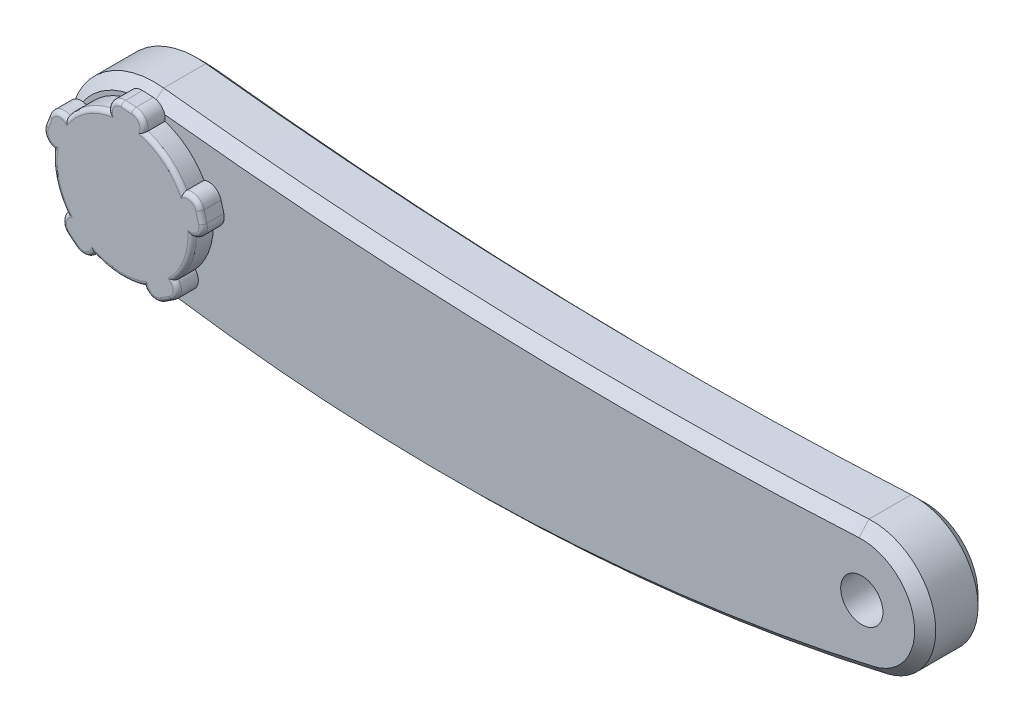
SolidWorks part; units mm, degrees
material "可锻铸铁"
ref_plane "前视基准面" through (0, 0, 0) normal (0, 0, 1) x (1, 0, 0)
ref_plane "上视基准面" through (0, 0, 0) normal (0, 1, 0) x (1, 0, 0)
ref_plane "右视基准面" through (0, 0, 0) normal (1, 0, 0) x (0, 0, -1)
sketch "草图1" plane through (0, 0, 0) normal (0, 0, 1) x (1, 0, 0)
  line L0 (-85, 0) -> (85, 0) construction
  circle A0 centre (-85, 0) radius 20
  circle A1 centre (85, 0) radius 15
  arc A2 (-82.7465, 19.8726) -> (84.1861, 14.9779) centre (29.9265, 1013.5048) ccw
  arc A3 (-88.3618, -19.7154) -> (88.3697, -14.6166) centre (-12.7206, 423.8817) ccw
  point P4 (0, 0)
  dimension "D2" = 30
  dimension "D3" = 40
  dimension "D4" = 450
  dimension "D5" = 1000
  dimension "D1" = 170
extrude "凸台-拉伸1" add sketch "草图1" along normal mid plane 15 contours A0 L0 A1 A2 | L0 A0 A3 A1 | A0 | A1 region at (-1.0237, 7.6812, 0) region at (-72.4659, -14.8523, 0) region at (-0.4487, -12.3679, 0) region at (74.4175, 10.0231, 0)
chamfer "倒角1" distance 2.5 angle 45 8 edges at (99.8523, 2.0996, -7.5) (0.6174, 13.9344, -7.5) (-104.8018, 2.8087, -7.5) (0.2568, -25.9311, -7.5) (-104.8018, 2.8087, 7.5) (0.6174, 13.9344, 7.5) (99.8523, 2.0996, 7.5) (0.2568, -25.9311, 7.5)
sketch "草图3" plane through (0, 0, 7.5) normal (0, 0, 1) x (1, 0, 0)
  circle A0 centre (-85, 0) radius 16.5
  dimension "D1" = 33
extrude "凸台-拉伸2" add sketch "草图3" along normal blind 5
sketch "草图4" plane through (0, 0, 12.5) normal (0, 0, 1) x (1, 0, 0)
  line L0 (-85, 0) -> (-71.0654, 8.0452)
  line L1 (-66.6676, 6.2235) -> (-66.0119, 3.7765)
  line L2 (-68.9097, 0) -> (-85, 0)
  line L3 (-85, 0) -> (-66.3397, 5) construction
  line L4 (-80.0278, -15.3028) -> (-85, 0)
  line L5 (-85, 0) -> (-73.0426, -10.7665)
  line L6 (-73.416, -15.512) -> (-75.5407, -16.8918)
  line L7 (-98.0173, -9.4577) -> (-85, 0)
  line L8 (-85, 0) -> (-91.5445, -14.6992)
  line L9 (-96.1731, -15.8105) -> (-98.142, -14.2161)
  line L10 (-98.0173, 9.4577) -> (-85, 0)
  line L11 (-85, 0) -> (-101.0022, 1.6819)
  line L12 (-103.4893, 5.7406) -> (-102.5814, 8.1057)
  line L13 (-80.0278, 15.3028) -> (-85, 0)
  line L14 (-85, 0) -> (-88.3454, 15.7387)
  line L15 (-85.2539, 19.3583) -> (-82.724, 19.2257)
  arc A0 (-68.9097, 0) -> (-66.0119, 3.7765) centre (-68.9097, 3) ccw
  arc A1 (-66.6676, 6.2235) -> (-71.0654, 8.0452) centre (-69.5654, 5.4471) ccw
  arc A2 (-80.0278, -15.3028) -> (-75.5407, -16.8918) centre (-77.1746, -14.3758) ccw
  arc A3 (-73.416, -15.512) -> (-73.0426, -10.7665) centre (-75.05, -12.996) ccw
  arc A4 (-98.0173, -9.4577) -> (-98.142, -14.2161) centre (-96.254, -11.8847) ccw
  arc A5 (-96.1731, -15.8105) -> (-91.5445, -14.6992) centre (-94.2852, -13.479) ccw
  arc A6 (-98.0173, 9.4577) -> (-102.5814, 8.1057) centre (-99.7807, 7.0306) ccw
  arc A7 (-103.4893, 5.7406) -> (-101.0022, 1.6819) centre (-100.6886, 4.6655) ccw
  arc A8 (-80.0278, 15.3028) -> (-82.724, 19.2257) centre (-82.881, 16.2299) ccw
  arc A9 (-85.2539, 19.3583) -> (-88.3454, 15.7387) centre (-85.4109, 16.3624) ccw
  circle A10 centre (-85, 0) radius 2
  point P12 (-67.6795, 10)
  point P36 (-85, 0)
  circle M5 centre (-85, 0) radius 16.5
  dimension "D3" = 3
  dimension "D5" = 4
  dimension "D1" = 30
  dimension "D2" = 20
  dimension "D4" = 5
extrude "凸台-拉伸3" add sketch "草图4" against normal blind 5 contours A10 L13 A8 A9 L14 M5 | L15 A9 A8 M5 | L3 L1 A1 M5 | L3 A0 L1 M5 | L3 A10 L2 A0 M5 | A10 L3 A1 L0 M5 | A10 L4 A2 A3 L5 M5 | L6 A3 A2 M5 | L9 A5 A4 M5 | A10 L7 A4 A5 L8 M5 | A10 L10 A6 A7 L11 M5 | L12 A7 A6 M5 region at (-74.734, 4.2521, 12.5) region at (-73.9833, 1.4506, 12.5) region at (-78.9998, -9.2394, 12.5) region at (-91.9331, -8.5616, 12.5) region at (-95.285, 3.9481, 12.5) region at (-84.4234, 11.0017, 12.5) region at (-68.4431, 6.4563, 12.5) region at (-67.4332, 2.6871, 12.5) region at (-75.3796, -14.8141, 12.5) region at (-96.1162, -13.7273, 12.5) region at (-101.4905, 6.3301, 12.5) region at (-84.0756, 17.6395, 12.5)
fillet "圆角4" radius 1 20 edges at (-87.5535, 18.4623, 12.5) (-83.9889, 19.292, 12.5) (-80.5307, 18.0943, 12.5) (-74.6162, 12.8229, 12.5) (-68.2303, 8.1337, 12.5) (-66.3397, 5, 12.5) (-66.4102, 1.3409, 12.5) (-69.5959, -5.9131, 12.5) (-72.0823, -13.4355, 12.5) (-74.4784, -16.2019, 12.5) (-77.9802, -17.2656, 12.5) (-85.8635, -16.4774, 12.5) (-93.7861, -16.4372, 12.5) (-97.1575, -15.0133, 12.5) (-99.2513, -12.0116, 12.5) (-100.9378, -4.2705, 12.5) (-103.3478, 3.2767, 12.5) (-103.0354, 6.9231, 12.5) (-100.8276, 9.842, 12.5) (-93.9865, 13.8381, 12.5)
sketch "草图5" plane through (0, 0, 7.5) normal (0, 0, 1) x (1, 0, 0)
  circle A0 centre (85, 0) radius 5
  dimension "D1" = 10
extrude "切除-拉伸1" cut sketch "草图5" against normal blind 10
sketch "草图6" plane through (0, 0, -7.5) normal (0, 0, -1) x (-1, 0, 0)
  circle A0 centre (85, 0) radius 5
  dimension "D1" = 10
extrude "凸台-拉伸4" add sketch "草图6" along normal blind 10
